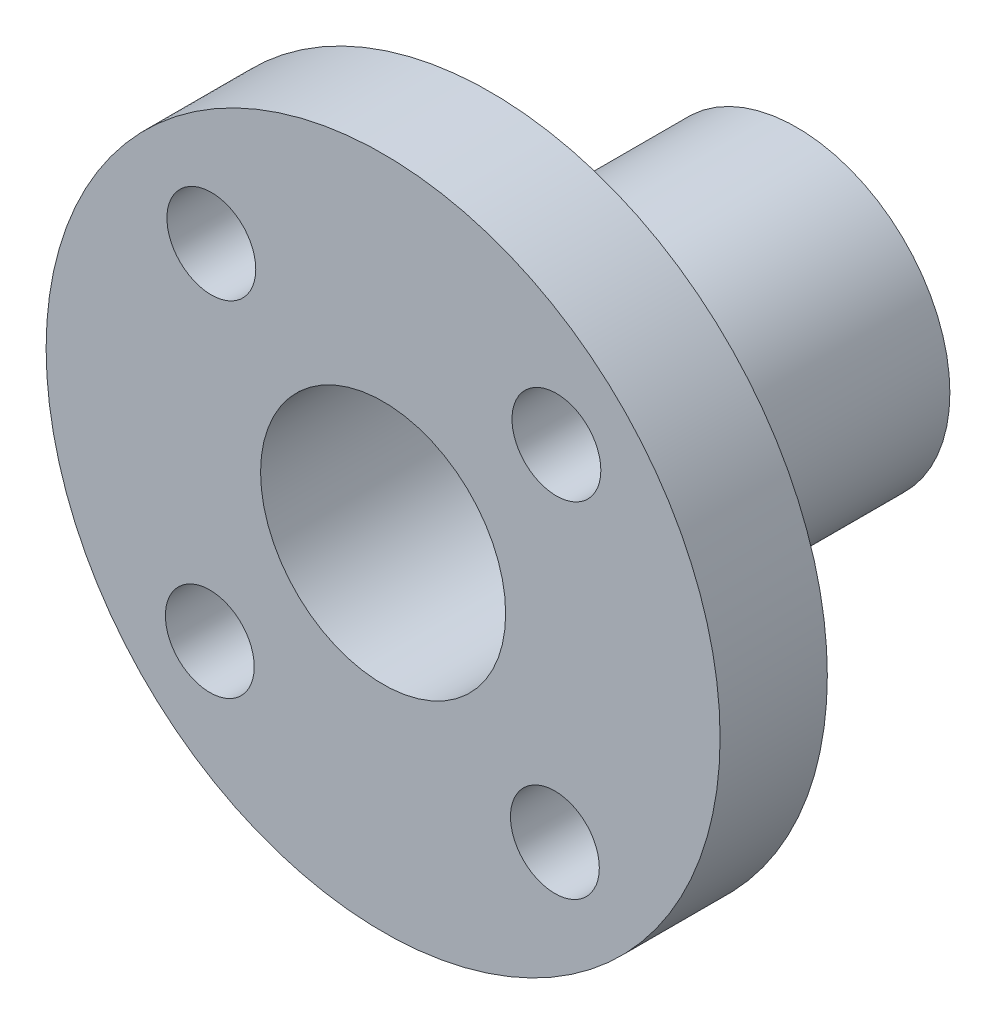
SolidWorks part; units mm, degrees
material "Fósforo-bronze  10% D, UNS C52400"
ref_plane "Front Plane" through (0, 0, 0) normal (0, 0, 1) x (1, 0, 0)
ref_plane "Top Plane" through (0, 0, 0) normal (0, 1, 0) x (1, 0, 0)
ref_plane "Right Plane" through (0, 0, 0) normal (1, 0, 0) x (0, 0, -1)
sketch "Sketch1" plane through (0, 0, 0) normal (0, 0, 1) x (1, 0, 0)
  circle A0 centre (0.05, 219.95) radius 11
  circle A1 centre (0.05, 219.95) radius 4
  circle A2 centre (5.6569, 214.2931) radius 1.45
  circle A3 centre (-5.6069, 214.3431) radius 1.45
  circle A4 centre (-5.5569, 225.6069) radius 1.45
  circle A5 centre (5.7069, 225.5569) radius 1.45
  point P16 (0.05, 219.95)
  dimension "D1" = 4
extrude "Boss-Extrude1" add sketch "Sketch1" along normal blind 3.5 contours A0 A5 A4 A3 A2 A1 region at (-10.6389, 219.95, 0)
sketch "Sketch2" plane through (0, 0, 0) normal (0, 0, -1) x (-1, 0, 0)
  circle A0 centre (-0.05, 219.95) radius 5
  circle A1 centre (-0.05, 219.95) radius 4
  dimension "D1" = 10
  dimension "D2" = 8
extrude "Boss-Extrude2" add sketch "Sketch2" along normal blind 10
